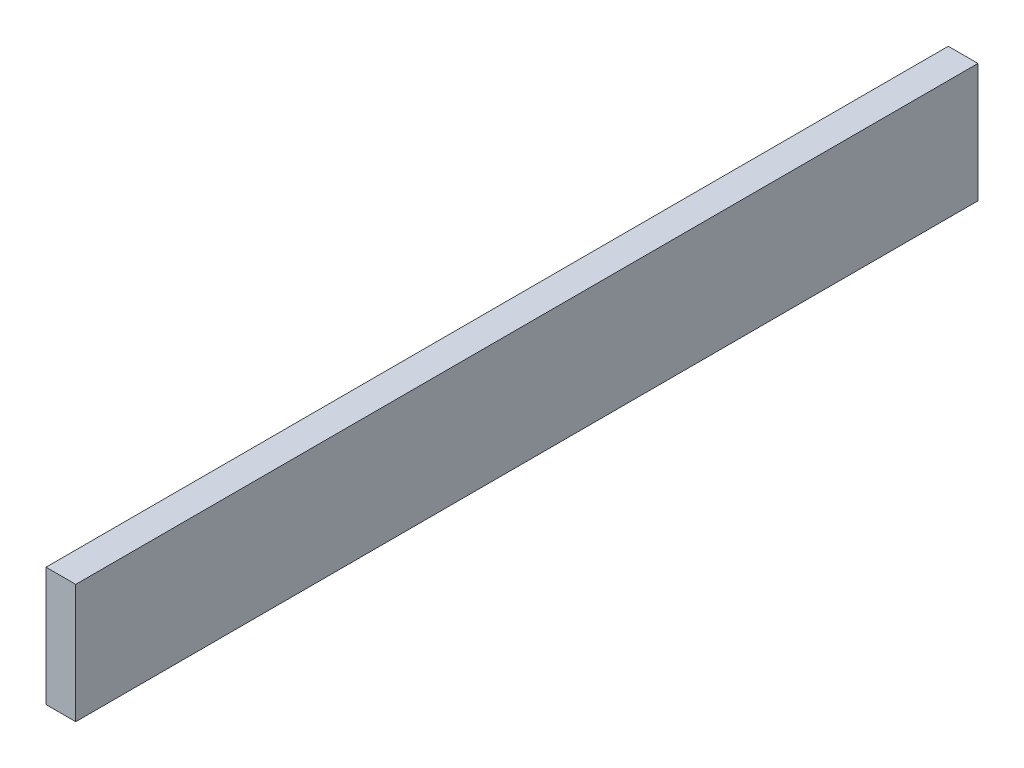
SolidWorks part; units mm, degrees
ref_plane "Front" through (0, 0, 0) normal (0, 0, 1) x (1, 0, 0)
ref_plane "Top" through (0, 0, 0) normal (0, 1, 0) x (1, 0, 0)
ref_plane "Right" through (0, 0, 0) normal (1, 0, 0) x (0, 0, -1)
sketch "Sketch1" plane through (0, 0, 0) normal (0, 1, 0) x (1, 0, 0)
  line L1 (0, 0) -> (76.2, 0)
  line L2 (0, 0) -> (0, 2311.4)
  line L3 (0, 2311.4) -> (76.2, 2311.4)
  line L4 (76.2, 0) -> (76.2, 2311.4)
  dimension "D1" = 2311.4
  dimension "D2" = 76.2
extrude "Boss-Extrude1" add sketch "Sketch1" along normal blind 304.8
